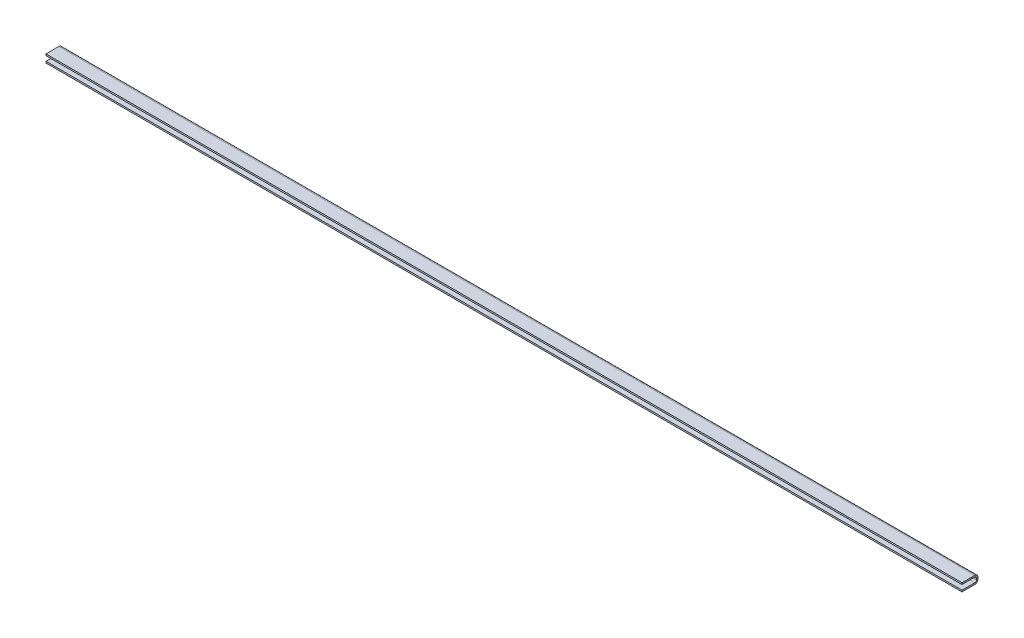
SolidWorks part; units mm, degrees
note: The reader was unsure of these and kept them because the rebuilt part matched: flange length of "边线-法兰1".
ref_plane "前视基准面" through (0, 0, 0) normal (0, 0, 1) x (1, 0, 0)
ref_plane "上视基准面" through (0, 0, 0) normal (0, 1, 0) x (1, 0, 0)
ref_plane "右视基准面" through (0, 0, 0) normal (1, 0, 0) x (0, 0, -1)
sketch "草图1" plane through (0, 0, 0) normal (0, 0, 1) x (1, 0, 0)
  line L1 (-572, 5) -> (572, 5)
  line L2 (-572, 5) -> (-572, -5)
  line L3 (-572, -5) -> (572, -5)
  line L4 (572, 5) -> (572, -5)
  line L5 (-572, 5) -> (572, -5) construction
  line L6 (-572, -5) -> (572, 5) construction
  point P0 (0, 0)
  dimension "D1" = 10
  dimension "D2" = 1144
base flange "基体-法兰1" sketch "草图1" thickness 2 reverse thickness direction no parameters "D1"=2
edge flange "边线-法兰1" sketch "草图10" flange profiles "草图10", "草图11" flange angle 90 flange length 20 flange position material inside bend radius 2 thickness 2 relief rectangular parameters "D6"=10, "D8"=1
sketch "草图10" plane through (0, 5, 0) normal (0, 1, 0) x (-1, 0, 0)
  line L0 (-572, 0) -> (572, 0) construction
  line L1 (-572, 0) -> (572, 0)
  line L2 (-572, 0) -> (-572, 18)
  line L3 (-572, 18) -> (572, 18)
  line L4 (572, 18) -> (572, 0)
sketch "草图11" plane through (0, -5, 0) normal (0, -1, 0) x (1, 0, 0)
  line L0 (-572, 0) -> (572, 0) construction
  line L1 (-572, 0) -> (572, 0)
  line L2 (-572, 0) -> (-572, 18)
  line L3 (-572, 18) -> (572, 18)
  line L4 (572, 18) -> (572, 0)
bend "边线折弯1" bend radius 2 bend angle 90 parameters "D5"=1
bend "边线折弯2" bend radius 2 bend angle 90 parameters "D5"=2
sketch "折弯-线1" plane through (0, 0, 0) normal (0, 1, 0) x (1, 0, 0)
sketch "边界框1" plane through (0, 0, 0) normal (0, 1, 0) x (1, 0, 0)
sheet metal parameters "钣金6" thickness 2 parameters "D1"=2
flat pattern "平板型式6" [suppressed]
sketch "折弯-线2" plane through (0, 0, 0) normal (0, 1, 0) x (1, 0, 0)
sketch "边界框2" [suppressed] plane through (0, 0, 0) normal (0, 1, 0) x (1, 0, 0)
sheet metal parameters "钣金7" thickness 2 parameters "D1"=2
flat pattern "平板型式6" [suppressed]
sketch "折弯-线2" plane through (0, 0, 0) normal (0, 1, 0) x (1, 0, 0)
sketch "边界框2" [suppressed] plane through (0, 0, 0) normal (0, 1, 0) x (1, 0, 0)
bend of the flat pattern "展开-<边线折弯1>1"
bend of the flat pattern "展开-<边线折弯2>1"
